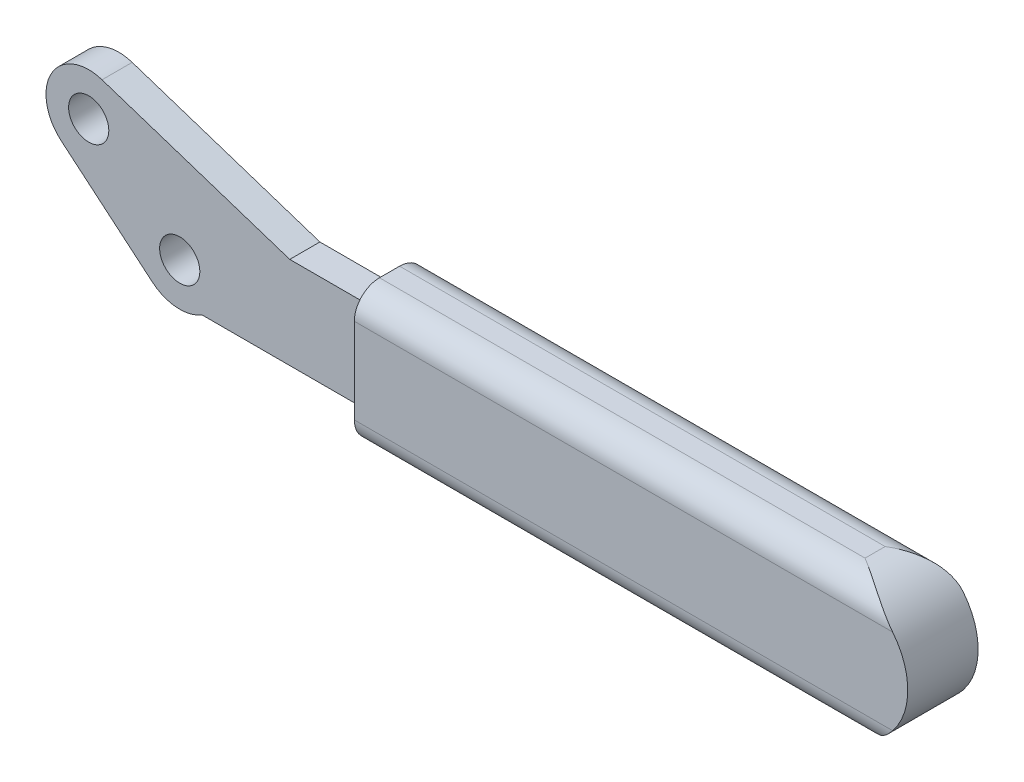
SolidWorks part; units mm, degrees
ref_plane "前视基准面" through (0, 0, 0) normal (0, 0, 1) x (1, 0, 0)
ref_plane "上视基准面" through (0, 0, 0) normal (0, 1, 0) x (1, 0, 0)
ref_plane "右视基准面" through (0, 0, 0) normal (1, 0, 0) x (0, 0, -1)
ref_plane "基准面1" through (0, 0, 0) normal (0, 0, 1) x (1, 0, 0)
sketch "草图1" plane through (0, 0, 0) normal (0, 0, 1) x (1, 0, 0)
  line L0 (-23.5898, 8.7473) -> (-5.474, -6.5027)
  line L1 (4.4371, -7.25) -> (38.75, -7.25)
  line L2 (38.75, -7.25) -> (38.75, 11.05)
  line L3 (38.75, 11.05) -> (21.8949, 11.05)
  line L4 (21.8949, 11.05) -> (-15.4624, 23.3252)
  arc A0 (-15.4624, 23.3252) -> (-23.5898, 8.7473) centre (-18.1158, 15.25) ccw
  arc A1 (-5.474, -6.5027) -> (4.4371, -7.25) centre (0, 0) ccw
  circle A2 centre (0, 0) radius 4
  circle A3 centre (-18.1158, 15.25) radius 4
extrude "凸台-拉伸1" add sketch "草图1" against normal blind 3 and the other way blind 3
ref_plane "基准面2" through (38.75, 0, 0) normal (1, 0, 0) x (0, 0, -1)
sketch "草图2" plane through (38.75, 0, 0) normal (1, 0, 0) x (0, 0, -1)
  line L0 (-7, 10.81) -> (-7, -6.19)
  line L1 (-2, -11.19) -> (2, -11.19)
  line L2 (7, -6.19) -> (7, 10.81)
  line L3 (2, 15.81) -> (-2, 15.81)
  arc A0 (-7, -6.19) -> (-2, -11.19) centre (-2, -6.19) ccw
  arc A1 (2, -11.19) -> (7, -6.19) centre (2, -6.19) ccw
  arc A2 (7, 10.81) -> (2, 15.81) centre (2, 10.81) ccw
  arc A3 (-2, 15.81) -> (-7, 10.81) centre (-2, 10.81) ccw
extrude "凸台-拉伸2" add sketch "草图2" along normal blind 110.134
ref_plane "基准面3" through (0, 0, 0) normal (0, 0, 1) x (1, 0, 0)
sketch "草图3" plane through (0, 0, 0) normal (0, 0, 1) x (1, 0, 0)
  line L0 (38.75, 15.81) -> (135.384, 15.81)
  line L1 (58.9398, -11.19) -> (38.75, -11.19)
  line L2 (38.75, -11.19) -> (38.75, -16.19)
  line L3 (38.75, -16.19) -> (153.884, -16.19)
  line L4 (153.884, -16.19) -> (153.884, 20.81)
  line L5 (153.884, 20.81) -> (38.75, 20.81)
  line L6 (38.75, 20.81) -> (38.75, 15.81)
  arc A0 (135.384, 15.81) -> (135.9106, -11.1797) centre (135.384, 2.31) cw
  arc A1 (135.9106, -11.1797) -> (134.9327, -11.0558) centre (135.7936, -8.182) cw
  arc A2 (134.9327, -11.0558) -> (117.1831, -10.8781) centre (125.75, -41.71) ccw
  arc A3 (117.1831, -10.8781) -> (115.5769, -10.8781) centre (116.38, -7.9876) cw
  arc A4 (115.5769, -10.8781) -> (98.2054, -10.9451) centre (107.01, -41.71) ccw
  arc A5 (98.2054, -10.9451) -> (96.5546, -10.9451) centre (97.38, -8.0609) cw
  arc A6 (96.5546, -10.9451) -> (79.1831, -10.8781) centre (87.75, -41.71) ccw
  arc A7 (79.1831, -10.8781) -> (77.5769, -10.8781) centre (78.38, -7.9876) cw
  arc A8 (77.5769, -10.8781) -> (59.8029, -11.0631) centre (69.01, -41.71) ccw
  arc A9 (59.8029, -11.0631) -> (58.9398, -11.19) centre (58.9398, -8.19) cw
extrude "切除-拉伸1" cut sketch "草图3" along normal blind 7 and the other way blind 7
ref_plane "基准面4" through (0, 0, 0) normal (0, 0, 1) x (1, 0, 0)
ref_plane "cp3 XY" through (0, 0, 0) normal (0, 0, 1) x (1, 0, 0)
ref_plane "cp3 XZ" through (0, 15.25, 0) normal (0, -1, 0) x (-1, 0, 0)
ref_plane "cp3 YZ" through (-18.1158, 0, 0) normal (1, 0, 0) x (0, 0, -1)
ref_axis "cp3 X" through (-80.9, 15.25, 0) along (1, 0, 0)
ref_axis "cp3 Y" through (-18.1158, -50, 0) along (0, 1, 0)
ref_axis "cp3 Z" through (-18.1158, 15.25, 80.9) along (0, 0, -1)
sketch3d "cp3"
  point P0 (-18.1158, 15.25, 0)
ref_plane "cp4 XY" through (0, 0, 0) normal (0, 0, 1) x (1, 0, 0)
ref_plane "cp4 XZ" through (0, 0, 0) normal (0, -1, 0) x (-1, 0, 0)
ref_plane "cp4 YZ" through (0, 0, 0) normal (1, 0, 0) x (0, 0, -1)
ref_axis "cp4 X" through (-80.9, 0, 0) along (1, 0, 0)
ref_axis "cp4 Y" through (0, -50, 0) along (0, 1, 0)
ref_axis "cp4 Z" through (0, 0, 80.9) along (0, 0, -1)
sketch3d "cp4"
  point P0 (0, 0, 0)
equation "\"零件重量\"= \"SW-质量\""
